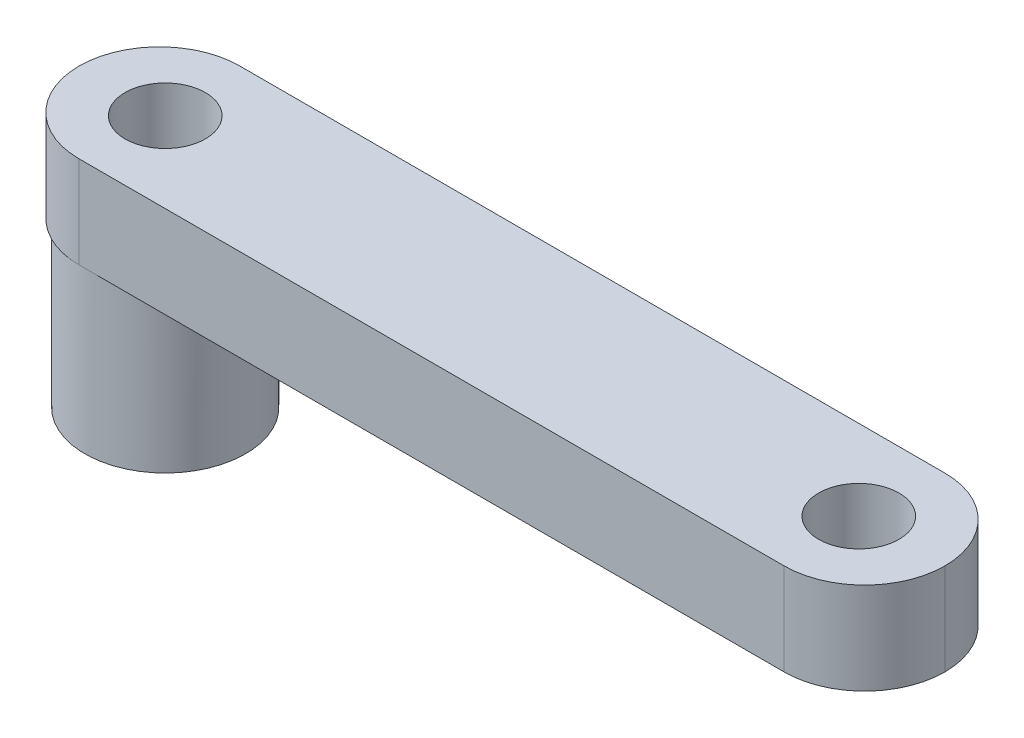
SolidWorks part; units mm, degrees
ref_plane "Front Plane" through (0, 0, 0) normal (0, 0, 1) x (1, 0, 0)
ref_plane "Top Plane" through (0, 0, 0) normal (0, 1, 0) x (1, 0, 0)
ref_plane "Right Plane" through (0, 0, 0) normal (1, 0, 0) x (0, 0, -1)
sketch "Sketch1" plane through (0, 0, 0) normal (0, 1, 0) x (1, 0, 0)
  line L1 (-18.85, 3.5) -> (18.85, 3.5)
  line L2 (-18.85, 3.5) -> (-18.85, -3.5)
  line L3 (-18.85, -3.5) -> (18.85, -3.5)
  line L4 (18.85, 3.5) -> (18.85, -3.5)
  line L5 (-18.85, 3.5) -> (18.85, -3.5) construction
  line L6 (-18.85, -3.5) -> (18.85, 3.5) construction
  point P0 (0, 0)
  dimension "D1" = 7
  dimension "D2" = 37.7
extrude "Boss-Extrude1" add sketch "Sketch1" along normal blind 4
sketch "Sketch2" plane through (0, 4, 0) normal (0, 1, 0) x (1, 0, 0)
  line L0 (0, 0) -> (15.1, 0) construction
  line L1 (0, 0) -> (-15.1, 0) construction
  circle A0 centre (-15.1, 0) radius 1.75
  circle A1 centre (15.1, 0) radius 1.75
  dimension "D3" = 3.5
  dimension "D4" = 3.5
  dimension "D1" = 15.1
  dimension "D2" = 15.1
extrude "Cut-Extrude1" cut sketch "Sketch2" against normal through all
sketch "Sketch3" plane through (0, 0, 0) normal (0, -1, 0) x (1, 0, 0)
  circle A0 centre (-15.1, 0) radius 3.5
  circle A1 centre (-15.1, 0) radius 1.75 construction
  circle A2 centre (-15.1, 0) radius 1.75
  dimension "D1" = 7
extrude "Boss-Extrude2" add sketch "Sketch3" along normal blind 7
fillet "Fillet1" radius 3.5 4 edges at (18.85, 2, -3.5) (18.85, 2, 3.5) (-18.85, 2, -3.5) (-18.85, 2, 3.5)
